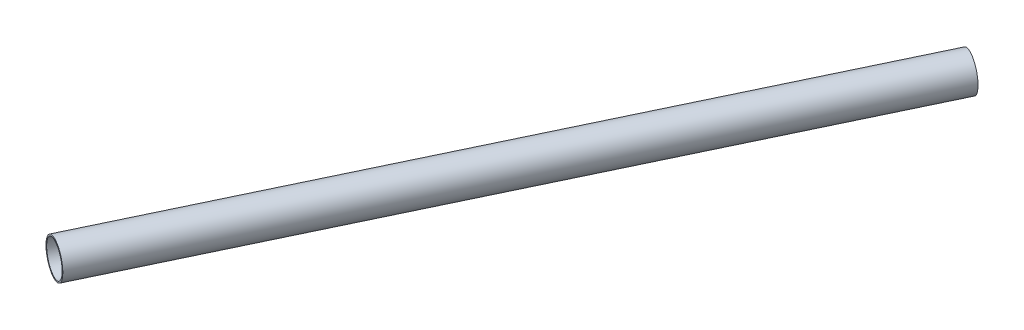
SolidWorks part; units mm, degrees
ref_plane "Front Plane" through (0, 0, 0) normal (0, 0, 1) x (1, 0, 0)
ref_plane "Top Plane" through (0, 0, 0) normal (0, 1, 0) x (1, 0, 0)
ref_plane "Right Plane" through (0, 0, 0) normal (1, 0, 0) x (0, 0, -1)
sketch "Sketch1" plane through (0, 0, 0) normal (0, 1, 0) x (1, 0, 0)
  line L0 (0, 0) -> (640, 0) construction
  line L1 (0, 0) -> (591.2829, 244.9174)
  line L2 (0, 0) -> (591.2829, -244.9174)
  line L3 (0, 0) -> (244.9174, -591.2829)
  line L4 (0, 0) -> (-244.9174, -591.2829)
  line L5 (0, 0) -> (-591.2829, -244.9174)
  line L6 (0, 0) -> (-591.2829, 244.9174)
  line L7 (0, 0) -> (-244.9174, 591.2829)
  line L8 (0, 0) -> (244.9174, 591.2829)
  line L9 (0, 145) -> (55, 145) construction
  line L10 (0, 0) -> (100, 0) construction
  line L11 (0, 0) -> (0, 145) construction
  line L14 (100, 0) -> (100, 145) construction
  circle A0 centre (0, 0) radius 640 construction
  point P15 (0, 0)
  dimension "D1" = 1280
  dimension "D2" = 22.5
  dimension "D4" = 145
  dimension "D5" = 100
  dimension "D6" = 55
  dimension "D3" = 8
sketch "Sketch2" plane through (0, 0, 0) normal (0, 1, 0) x (1, 0, 0)
  line L0 (-486.9956, 169.5033) -> (-66.9956, 169.5033) construction
  line L1 (-188.7141, -86.1278) -> (-188.7141, 241.8722) construction
  line L2 (525.6625, -1048.8053) -> (466.9027, -726.1115) construction
sketch "Sketch3" plane through (0, 0, 0) normal (0, 1, 0) x (1, 0, 0)
  line L0 (0, 0) -> (381.2468, 0) construction
  line L5 (0, 0) -> (0, 199.4415) construction
  line L6 (-10.2736, 158.9263) -> (10.2736, 158.9263)
  line L7 (10.2736, 158.9263) -> (13.1995, 163.9003)
  line L8 (13.1995, 163.9003) -> (45.5131, 148.2994)
  line L9 (45.5131, 148.2994) -> (66.2904, 80.9335)
  line L10 (66.2904, 80.9335) -> (73.8622, 80.9335)
  line L11 (73.8622, 80.9335) -> (86.8684, 42.4396)
  line L12 (86.8684, 42.4396) -> (86.8684, 30.0712)
  line L13 (86.8684, 30.0712) -> (81.3965, 24.5993)
  line L14 (81.3965, 24.5993) -> (81.3965, -24.5993)
  line L15 (-5.8349, 67.4929) -> (5.8349, 67.4929) construction
  line L16 (16.6008, 64.1674) -> (16.6008, 27.6557) construction
  line L17 (16.6008, 27.6557) -> (13.2646, 22.809) construction
  line L18 (13.2646, 22.809) -> (13.2646, -22.809) construction
  line L19 (5.8349, 128.0146) -> (5.8349, 107.4452)
  line L22 (5.8349, 107.4452) -> (9.2702, 107.4452)
  line L25 (9.2702, 107.4452) -> (10.663, 103.7163)
  line L26 (10.663, 103.7163) -> (20.7578, 101.0699)
  line L27 (20.7578, 101.0699) -> (32.199, 111.7601)
  line L28 (32.199, 111.7601) -> (32.199, 123.5038)
  line L29 (32.199, 123.5038) -> (24.9078, 123.5038)
  line L30 (24.9078, 123.5038) -> (13.8412, 132.5856)
  line L31 (13.8412, 132.5856) -> (9.2702, 132.5856)
  line L32 (9.2702, 132.5856) -> (5.8349, 128.0146)
  line L33 (41.9414, 39.7891) -> (51.4866, 54.1602)
  line L34 (51.4866, 54.1602) -> (55.4027, 54.1602)
  line L35 (55.4027, 54.1602) -> (58.1637, 51.3993)
  line L36 (58.1637, 51.3993) -> (58.1637, 43.1872)
  line L37 (58.1637, 43.1872) -> (66.3555, 28.462)
  line L38 (66.3555, 28.462) -> (66.3555, 24.0728)
  line L39 (66.3555, 24.0728) -> (62.2596, 17.9061)
  line L40 (62.2596, 17.9061) -> (47.8497, 18.1669)
  line L41 (47.8497, 18.1669) -> (41.9414, 27.1878)
  line L42 (41.9414, 27.1878) -> (41.9414, 39.7891)
  line L43 (-41.9414, 27.1878) -> (-41.9414, 39.7891)
  line L44 (-47.8497, 18.1669) -> (-41.9414, 27.1878)
  line L45 (-62.2596, 17.9061) -> (-47.8497, 18.1669)
  line L46 (-66.3555, 24.0728) -> (-62.2596, 17.9061)
  line L47 (-66.3555, 28.462) -> (-66.3555, 24.0728)
  line L48 (-58.1637, 43.1872) -> (-66.3555, 28.462)
  line L49 (-58.1637, 51.3993) -> (-58.1637, 43.1872)
  line L50 (-55.4027, 54.1602) -> (-58.1637, 51.3993)
  line L51 (-51.4866, 54.1602) -> (-55.4027, 54.1602)
  line L52 (-41.9414, 39.7891) -> (-51.4866, 54.1602)
  line L53 (-9.2702, 132.5856) -> (-5.8349, 128.0146)
  line L54 (-13.8412, 132.5856) -> (-9.2702, 132.5856)
  line L55 (-24.9078, 123.5038) -> (-13.8412, 132.5856)
  line L56 (-32.199, 123.5038) -> (-24.9078, 123.5038)
  line L57 (-32.199, 111.7601) -> (-32.199, 123.5038)
  line L58 (-20.7578, 101.0699) -> (-32.199, 111.7601)
  line L59 (-10.663, 103.7163) -> (-20.7578, 101.0699)
  line L60 (-9.2702, 107.4452) -> (-10.663, 103.7163)
  line L61 (-5.8349, 107.4452) -> (-9.2702, 107.4452)
  line L62 (-5.8349, 128.0146) -> (-5.8349, 107.4452)
  line L63 (-13.2646, 22.809) -> (-13.2646, -22.809) construction
  line L64 (-16.6008, 27.6557) -> (-13.2646, 22.809) construction
  line L65 (-16.6008, 64.1674) -> (-16.6008, 27.6557) construction
  line L66 (-81.3965, 24.5993) -> (-81.3965, -24.5993)
  line L67 (-86.8684, 30.0712) -> (-81.3965, 24.5993)
  line L68 (-86.8684, 42.4396) -> (-86.8684, 30.0712)
  line L69 (-73.8622, 80.9335) -> (-86.8684, 42.4396)
  line L70 (-66.2904, 80.9335) -> (-73.8622, 80.9335)
  line L71 (-45.5131, 148.2994) -> (-66.2904, 80.9335)
  line L72 (-13.1995, 163.9003) -> (-45.5131, 148.2994)
  line L73 (-10.2736, 158.9263) -> (-13.1995, 163.9003)
  line L74 (-10.2736, -158.9263) -> (-13.1995, -163.9003)
  line L75 (-13.1995, -163.9003) -> (-45.5131, -148.2994)
  line L76 (-45.5131, -148.2994) -> (-66.2904, -80.9335)
  line L77 (-66.2904, -80.9335) -> (-73.8622, -80.9335)
  line L78 (-73.8622, -80.9335) -> (-86.8684, -42.4396)
  line L79 (-86.8684, -42.4396) -> (-86.8684, -30.0712)
  line L80 (-86.8684, -30.0712) -> (-81.3965, -24.5993)
  line L81 (-16.6008, -64.1674) -> (-16.6008, -27.6557) construction
  line L82 (-16.6008, -27.6557) -> (-13.2646, -22.809) construction
  line L83 (-5.8349, -128.0146) -> (-5.8349, -107.4452)
  line L84 (-5.8349, -107.4452) -> (-9.2702, -107.4452)
  line L85 (-9.2702, -107.4452) -> (-10.663, -103.7163)
  line L86 (-10.663, -103.7163) -> (-20.7578, -101.0699)
  line L87 (-20.7578, -101.0699) -> (-32.199, -111.7601)
  line L88 (-32.199, -111.7601) -> (-32.199, -123.5038)
  line L89 (-32.199, -123.5038) -> (-24.9078, -123.5038)
  line L90 (-24.9078, -123.5038) -> (-13.8412, -132.5856)
  line L91 (-13.8412, -132.5856) -> (-9.2702, -132.5856)
  line L92 (-9.2702, -132.5856) -> (-5.8349, -128.0146)
  line L93 (-41.9414, -39.7891) -> (-51.4866, -54.1602)
  line L94 (-51.4866, -54.1602) -> (-55.4027, -54.1602)
  line L95 (-55.4027, -54.1602) -> (-58.1637, -51.3993)
  line L96 (-58.1637, -51.3993) -> (-58.1637, -43.1872)
  line L97 (-58.1637, -43.1872) -> (-66.3555, -28.462)
  line L98 (-66.3555, -28.462) -> (-66.3555, -24.0728)
  line L99 (-66.3555, -24.0728) -> (-62.2596, -17.9061)
  line L100 (-62.2596, -17.9061) -> (-47.8497, -18.1669)
  line L101 (-47.8497, -18.1669) -> (-41.9414, -27.1878)
  line L102 (-41.9414, -27.1878) -> (-41.9414, -39.7891)
  line L103 (41.9414, -27.1878) -> (41.9414, -39.7891)
  line L104 (47.8497, -18.1669) -> (41.9414, -27.1878)
  line L105 (62.2596, -17.9061) -> (47.8497, -18.1669)
  line L106 (66.3555, -24.0728) -> (62.2596, -17.9061)
  line L107 (66.3555, -28.462) -> (66.3555, -24.0728)
  line L108 (58.1637, -43.1872) -> (66.3555, -28.462)
  line L109 (58.1637, -51.3993) -> (58.1637, -43.1872)
  line L110 (55.4027, -54.1602) -> (58.1637, -51.3993)
  line L111 (51.4866, -54.1602) -> (55.4027, -54.1602)
  line L112 (41.9414, -39.7891) -> (51.4866, -54.1602)
  line L113 (9.2702, -132.5856) -> (5.8349, -128.0146)
  line L114 (13.8412, -132.5856) -> (9.2702, -132.5856)
  line L115 (24.9078, -123.5038) -> (13.8412, -132.5856)
  line L116 (32.199, -123.5038) -> (24.9078, -123.5038)
  line L117 (32.199, -111.7601) -> (32.199, -123.5038)
  line L118 (20.7578, -101.0699) -> (32.199, -111.7601)
  line L119 (10.663, -103.7163) -> (20.7578, -101.0699)
  line L120 (9.2702, -107.4452) -> (10.663, -103.7163)
  line L121 (5.8349, -107.4452) -> (9.2702, -107.4452)
  line L122 (5.8349, -128.0146) -> (5.8349, -107.4452)
  line L123 (16.6008, -27.6557) -> (13.2646, -22.809) construction
  line L124 (16.6008, -64.1674) -> (16.6008, -27.6557) construction
  line L125 (-5.8349, -67.4929) -> (5.8349, -67.4929) construction
  line L126 (86.8684, -30.0712) -> (81.3965, -24.5993)
  line L127 (86.8684, -42.4396) -> (86.8684, -30.0712)
  line L128 (73.8622, -80.9335) -> (86.8684, -42.4396)
  line L129 (66.2904, -80.9335) -> (73.8622, -80.9335)
  line L130 (45.5131, -148.2994) -> (66.2904, -80.9335)
  line L131 (13.1995, -163.9003) -> (45.5131, -148.2994)
  line L132 (10.2736, -158.9263) -> (13.1995, -163.9003)
  line L133 (-10.2736, -158.9263) -> (10.2736, -158.9263)
  line L134 (-5.3457, 68.4929) -> (5.3457, 68.4929)
  line L135 (17.6008, 64.1674) -> (17.6008, 27.3448)
  line L136 (17.6008, 27.3448) -> (14.2646, 22.498)
  line L137 (14.2646, 22.498) -> (14.2646, -22.498)
  line L138 (-17.6008, 64.1674) -> (-17.6008, 27.3448)
  line L139 (-17.6008, 27.3448) -> (-14.2646, 22.498)
  line L140 (-5.3457, 68.4929) -> (5.3457, 68.4929) construction
  line L141 (14.2646, 22.498) -> (14.2646, -22.498) construction
  line L142 (17.6008, -27.3448) -> (14.2646, -22.498) construction
  line L143 (17.6008, -64.1674) -> (17.6008, -27.3448) construction
  line L144 (-14.2646, 22.498) -> (-14.2646, -22.498)
  line L145 (17.6008, -64.1674) -> (17.6008, -27.3448)
  line L146 (17.6008, -27.3448) -> (14.2646, -22.498)
  line L147 (-17.6008, -27.3448) -> (-14.2646, -22.498)
  line L148 (-17.6008, -64.1674) -> (-17.6008, -27.3448)
  line L149 (-5.3457, -68.4929) -> (5.3457, -68.4929)
  arc A0 (5.8349, 67.4929) -> (16.6008, 64.0252) centre (10.663, 64.0364) cw construction
  arc A5 (-5.8349, 67.4929) -> (-16.6008, 64.0252) centre (-10.663, 64.0364) ccw construction
  arc A6 (-5.8349, -67.4929) -> (-16.6008, -64.0252) centre (-10.663, -64.0364) cw construction
  arc A7 (5.8349, -67.4929) -> (16.6008, -64.0252) centre (10.663, -64.0364) ccw construction
  arc A8 (-5.3457, 68.4929) -> (-17.6008, 64.0234) centre (-10.663, 64.0364) ccw
  arc A9 (5.3457, 68.4929) -> (17.6008, 64.0234) centre (10.663, 64.0364) cw
  arc A10 (-5.3457, 68.4929) -> (-17.6008, 64.0234) centre (-10.663, 64.0364) ccw construction
  arc A11 (5.3457, -68.4929) -> (17.6008, -64.0234) centre (10.663, -64.0364) ccw
  arc A12 (-5.3457, -68.4929) -> (-17.6008, -64.0234) centre (-10.663, -64.0364) cw
  ellipse E0 centre (11.3851, 149.6854) end of major axis (12.0553, 155.2702) minor radius 3.0047
  ellipse E1 centre (33.6925, 82.363) end of major axis (41.1096, 88.3895) minor radius 4.3287
  ellipse E2 centre (44.8955, 74.0187) end of major axis (51.4866, 79.374) minor radius 4.6847
  ellipse E3 centre (66.3555, 66.447) end of major axis (67.1471, 72.2416) minor radius 3.5711
  ellipse E4 centre (-66.3555, 66.447) end of major axis (-67.1471, 72.2416) minor radius 3.5711
  ellipse E5 centre (-44.8955, 74.0187) end of major axis (-51.4866, 79.374) minor radius 4.6847
  ellipse E6 centre (-33.6925, 82.363) end of major axis (-41.1096, 88.3895) minor radius 4.3287
  ellipse E7 centre (-11.3851, 149.6854) end of major axis (-12.0553, 155.2702) minor radius 3.0047
  ellipse E8 centre (-11.3851, -149.6854) end of major axis (-12.0553, -155.2702) minor radius 3.0047
  ellipse E9 centre (-33.6925, -82.363) end of major axis (-41.1096, -88.3895) minor radius 4.3287
  ellipse E10 centre (-44.8955, -74.0187) end of major axis (-51.4866, -79.374) minor radius 4.6847
  ellipse E11 centre (-66.3555, -66.447) end of major axis (-67.1471, -72.2416) minor radius 3.5711
  ellipse E12 centre (66.3555, -66.447) end of major axis (67.1471, -72.2416) minor radius 3.5711
  ellipse E13 centre (44.8955, -74.0187) end of major axis (51.4866, -79.374) minor radius 4.6847
  ellipse E14 centre (33.6925, -82.363) end of major axis (41.1096, -88.3895) minor radius 4.3287
  ellipse E15 centre (11.3851, -149.6854) end of major axis (12.0553, -155.2702) minor radius 3.0047
  point P117 (0, 67.4929)
  point P126 (0, 158.9263)
  point P180 (0, -158.9263)
  point P181 (0, -67.4929)
  point P190 (-81.3965, 0)
  point P193 (-13.2646, 0)
  point P234 (13.2646, 0)
  point P237 (81.3965, 0)
  point P261 (0, 68.4929)
  point P271 (14.2646, 0)
  point P274 (-14.2646, 0)
  dimension "D1" = 1
sketch "Sketch4" plane through (0, 0, 0) normal (0, 1, 0) x (1, 0, 0)
  line L0 (0, 0) -> (81.2255, 0) construction
  line L1 (0, 0) -> (0, 97.3086) construction
  line L2 (0, 0) -> (0, 199.4415) construction
  line L3 (-10.1399, 86.6928) -> (10.1399, 86.6928)
  line L4 (10.1399, 86.6928) -> (16.0235, 80.8091)
  line L5 (16.0235, 80.8091) -> (23.9736, 57.3032)
  line L6 (23.9736, 57.3032) -> (23.9736, 47.8894)
  line L7 (23.9736, 47.8894) -> (21.6776, 47.8894)
  line L8 (21.6776, 47.8894) -> (21.6776, 27.2256)
  line L9 (21.6776, 27.2256) -> (27.5382, 22.1416)
  line L10 (27.5382, 22.1416) -> (27.5382, 14.9676)
  line L11 (27.5382, 14.9676) -> (23.9736, 10.8585)
  line L12 (23.9736, 10.8585) -> (23.9736, -10.8585)
  line L13 (-23.9736, 10.8585) -> (-23.9736, -10.8585)
  line L14 (-27.5382, 14.9676) -> (-23.9736, 10.8585)
  line L15 (-27.5382, 22.1416) -> (-27.5382, 14.9676)
  line L16 (-21.6776, 27.2256) -> (-27.5382, 22.1416)
  line L17 (-21.6776, 47.8894) -> (-21.6776, 27.2256)
  line L18 (-23.9736, 47.8894) -> (-21.6776, 47.8894)
  line L19 (-23.9736, 57.3032) -> (-23.9736, 47.8894)
  line L20 (-16.0235, 80.8091) -> (-23.9736, 57.3032)
  line L21 (-10.1399, 86.6928) -> (-16.0235, 80.8091)
  line L22 (-10.1399, -86.6928) -> (-16.0235, -80.8091)
  line L23 (-16.0235, -80.8091) -> (-23.9736, -57.3032)
  line L24 (-23.9736, -57.3032) -> (-23.9736, -47.8894)
  line L25 (-23.9736, -47.8894) -> (-21.6776, -47.8894)
  line L26 (-21.6776, -47.8894) -> (-21.6776, -27.2256)
  line L27 (-21.6776, -27.2256) -> (-27.5382, -22.1416)
  line L28 (-27.5382, -22.1416) -> (-27.5382, -14.9676)
  line L29 (-27.5382, -14.9676) -> (-23.9736, -10.8585)
  line L30 (27.5382, -14.9676) -> (23.9736, -10.8585)
  line L31 (27.5382, -22.1416) -> (27.5382, -14.9676)
  line L32 (21.6776, -27.2256) -> (27.5382, -22.1416)
  line L33 (21.6776, -47.8894) -> (21.6776, -27.2256)
  line L34 (23.9736, -47.8894) -> (21.6776, -47.8894)
  line L35 (23.9736, -57.3032) -> (23.9736, -47.8894)
  line L36 (16.0235, -80.8091) -> (23.9736, -57.3032)
  line L37 (10.1399, -86.6928) -> (16.0235, -80.8091)
  line L38 (-10.1399, -86.6928) -> (10.1399, -86.6928)
  point P3 (0, -86.6928)
  point P27 (0, 86.6928)
  point P37 (-23.9736, 0)
  point P38 (23.9736, 0)
sketch "Sketch5" plane through (0, 0, 0) normal (0, 1, 0) x (1, 0, 0)
  line L0 (0, 68.4929) -> (0, 86.6928) construction
  line L1 (15.4511, 110) -> (223.3697, 546.0887)
  line L2 (0, 0) -> (0, 251.8084) construction
  line L3 (0, 110) -> (47.9221, 110) construction
  line L5 (244.9174, 616.9519) -> (262.4572, 609.0616) construction
  line L6 (262.4572, 609.0616) -> (269.1565, 599.6825) construction
  line L7 (269.1565, 599.6825) -> (256.4381, 571.4103) construction
  line L8 (256.4381, 571.4103) -> (244.9174, 563.1812) construction
  line L9 (244.9174, 563.1812) -> (221.08, 517.0826) construction
  line L10 (221.08, 517.0826) -> (201.6817, 527.1134) construction
  line L11 (201.6817, 527.1134) -> (221.6088, 571.4103) construction
  line L12 (221.6088, 571.4103) -> (218.2415, 584.6462) construction
  line L13 (218.2415, 584.6462) -> (232.4366, 616.2011) construction
  line L14 (232.4366, 616.2011) -> (244.9174, 616.9519) construction
  line L15 (244.9174, 591.2829) -> (309.3694, 564.586) construction
  line L16 (269.6266, 526.9284) -> (173.6132, 566.6985) construction
  line L18 (0, 0) -> (107.3069, 0) construction
  dimension "D1" = 110
  dimension "D2" = 50
sweep "Sweep1" add path "Sketch5" circular profile diameter 25 parameters "D3"=25
sweep "Cut-Sweep1" cut path "Sketch5<2>" circular profile diameter 23 parameters "D3"=23
sketch "Sketch5<2>" plane through (0, 0, 0) normal (0, 1, 0) x (1, 0, 0) same geometry as "Sketch5"
